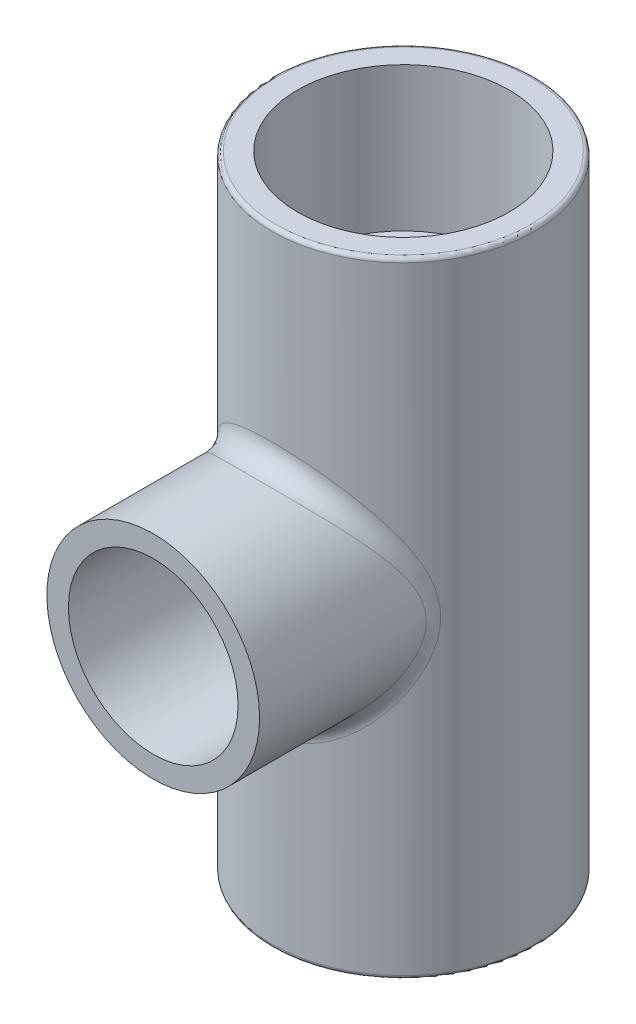
SolidWorks part; units mm, degrees
ref_plane "Front Plane" through (0, 0, 0) normal (0, 0, 1) x (1, 0, 0)
ref_plane "Top Plane" through (0, 0, 0) normal (0, 1, 0) x (1, 0, 0)
ref_plane "Right Plane" through (0, 0, 0) normal (1, 0, 0) x (0, 0, -1)
sketch "Sketch1" plane through (0, 0, 0) normal (0, 1, 0) x (1, 0, 0)
  circle A0 centre (0, 0) radius 412
  circle A1 centre (0, 0) radius 656.5
  dimension "D1" = 824
  dimension "D2" = 1313
extrude "Boss-Extrude1" add sketch "Sketch1" along normal blind 3125
sketch "Sketch2" plane through (0, 3125, 0) normal (0, 1, 0) x (1, 0, 0)
  circle A0 centre (0, 0) radius 529
  dimension "D1" = 1058
extrude "Cut-Extrude1" cut sketch "Sketch2" against normal blind 720
sketch "Sketch3" plane through (0, 0, 0) normal (0, -1, 0) x (1, 0, 0)
  circle A0 centre (0, 0) radius 529
  dimension "D1" = 1058
extrude "Cut-Extrude2" cut sketch "Sketch3" against normal blind 720
sketch "Sketch4" plane through (0, 0, 0) normal (0, 0, 1) x (1, 0, 0)
  line L0 (0, 0) -> (0, 1562.5) construction
  circle A0 centre (0, 1562.5) radius 311
  circle A1 centre (0, 1562.5) radius 531.5
  dimension "D1" = 622
  dimension "D2" = 1063
  dimension "D3" = 1562.5
extrude "Boss-Extrude3" add sketch "Sketch4" along normal blind 1250
sketch "Sketch14" plane through (0, 0, 1250) normal (0, 0, 1) x (1, 0, 0)
  circle A0 centre (0, 1562.5) radius 424
  dimension "D1" = 848
extrude "Cut-Extrude16" cut sketch "Sketch14" against normal blind 690
sketch "Sketch15" plane through (0, 3125, 0) normal (0, 1, 0) x (1, 0, 0)
  circle A0 centre (0, 0) radius 412
  dimension "D1" = 824
extrude "Cut-Extrude17" cut sketch "Sketch15" against normal through all
sketch "Sketch16" plane through (0, 0, 560) normal (0, 0, 1) x (1, 0, 0)
  circle A0 centre (0, 1562.5) radius 311
  dimension "D1" = 622
extrude "Cut-Extrude18" cut sketch "Sketch16" against normal blind 580
fillet "Fillet1" radius 100 1 edges at (524.4649, 1648.6906, 394.8782)
fillet "Fillet2" radius 20 1 edges at (0, 0, 656.5)
fillet "Fillet3" radius 20 1 edges at (0, 3125, 656.5)
